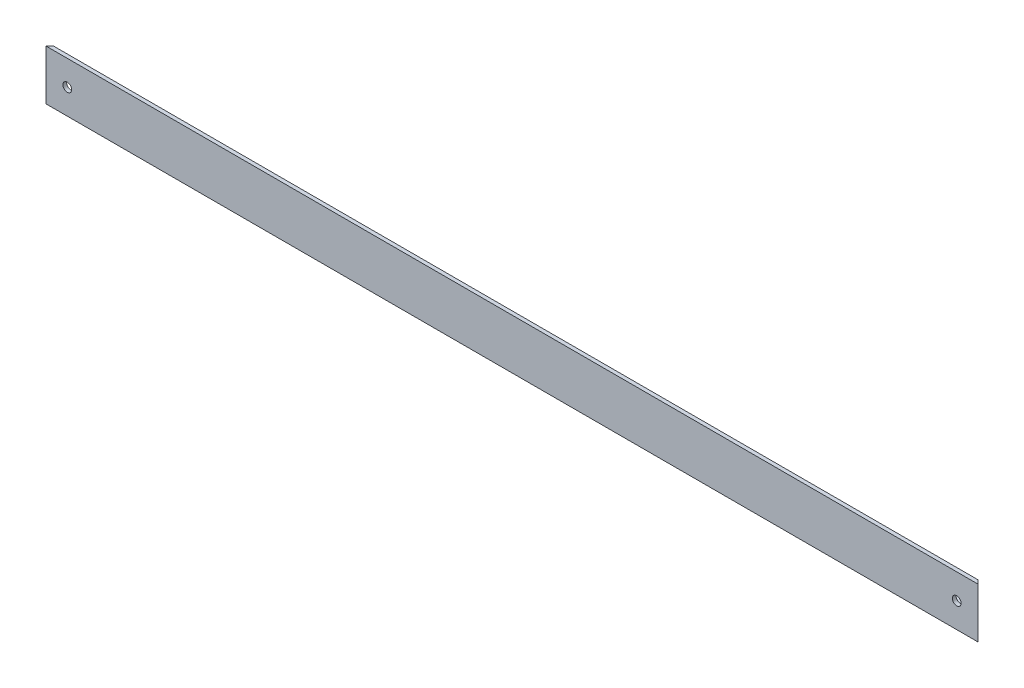
SolidWorks part; units mm, degrees
material "1060 Сплав"
ref_plane "Спереди" through (0, 0, 0) normal (0, 0, 1) x (1, 0, 0)
ref_plane "Сверху" through (0, 0, 0) normal (0, 1, 0) x (1, 0, 0)
ref_plane "Справа" through (0, 0, 0) normal (1, 0, 0) x (0, 0, -1)
sketch "Эскиз1" plane through (0, 0, 0) normal (1, 0, 0) x (0, 0, -1)
  line L0 (0, 0) -> (20, 0)
  line L1 (20, 0) -> (20, 1.5)
  line L2 (20, 1.5) -> (1.5, 1.5)
  line L3 (1.5, 1.5) -> (1.5, 20)
  line L4 (1.5, 20) -> (0, 20)
  line L5 (0, 20) -> (0, 0)
  dimension "D1" = 20
  dimension "D2" = 1.5
extrude "Бобышка-Вытянуть1" add sketch "Эскиз1" along normal blind 372
sketch "Эскиз2" plane through (0, 0, 0) normal (0, -1, 0) x (1, 0, 0)
  line L0 (0, 0) -> (0, -20)
  line L1 (0, -20) -> (20, -20)
  line L2 (372, -20) -> (0, -20) construction
  line L3 (20, -20) -> (0, 0)
extrude "Вырез-Вытянуть1" cut sketch "Эскиз2" against normal through all
sketch "Эскиз3" plane through (0, 0, 0) normal (0, 0, 1) x (1, 0, 0)
  line L0 (0, 20) -> (0, 0) construction
  circle A0 centre (8.5, 10) radius 1.75
  point P5 (0, 10)
  dimension "D1" = 3.5
  dimension "D2" = 8.5
extrude "Вырез-Вытянуть2" cut sketch "Эскиз3" against normal up to next
ref_plane "Плоскость1" through (186, 0, 0) normal (1, 0, 0) x (0, 0, -1)
mirror "Зеркальное отражение3" about plane through (186, 0, 0) normal (1, 0, 0) of "Вырез-Вытянуть2", "Вырез-Вытянуть1"
ref_axis "Ось1" through (0, 10, 0) along (1, 0, 0)
equation "\"ATX.Case.01.Dimension.2\"=375"
equation "\"D1@Эскиз1\" = \"ATX.Case.01.Profile.20.Width\""
equation "\"D2@Эскиз1\" = \"ATX.Case.01.Profile.20.Thickness\""
equation "\"D1@Бобышка-Вытянуть1\" = \"ATX.Case.01.Dimension.2\" - \"ATX.Case.01.Profile.20.Thickness\" * 2мм"
equation "\"ATX.Case.01.Profile.20.Width\"=20"
equation "\"ATX.Case.01.Profile.20.Thickness\" = 1.5"
equation "\"D2@Эскиз3\"= \"ATX.Case.01.Profile.20.Width\" / 2 - \"ATX.Case.01.Profile.20.Thickness\""
